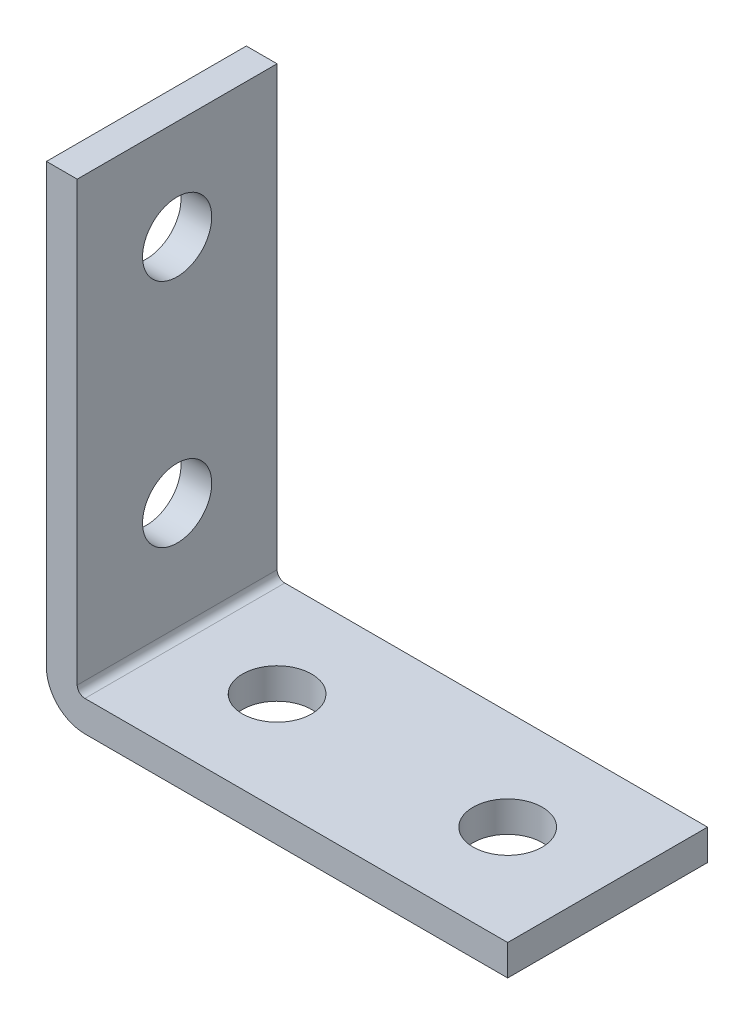
SolidWorks part; units mm, degrees
ref_plane "Front Plane" through (0, 0, 0) normal (0, 0, 1) x (1, 0, 0)
ref_plane "Top Plane" through (0, 0, 0) normal (0, 1, 0) x (1, 0, 0)
ref_plane "Right Plane" through (0, 0, 0) normal (1, 0, 0) x (0, 0, -1)
sketch "Sketch1" plane through (0, 0, 0) normal (0, 0, 1) x (1, 0, 0)
  line L0 (0, 98.425) -> (0, 7.9375)
  line L1 (7.9375, 0) -> (95.25, 0)
  arc A0 (0, 7.9375) -> (7.9375, 0) centre (7.9375, 7.9375) ccw
  dimension "D1" = 7.9375
  dimension "B" = 95.25
  dimension "A" = 98.425
extrude "Extrude-Thin1" add sketch "Sketch1" along normal mid plane 41.275 thin thin type one direction reverse wall 6.35
sketch "Sketch2" plane through (0, 6.35, 0) normal (0, 1, 0) x (1, 0, 0)
  line L0 (95.25, -20.6375) -> (95.25, 20.6375) construction
  circle A0 centre (74.6125, 0) radius 7.1438
  circle A1 centre (26.9875, 0) radius 7.1437
  dimension "Hole Size" = 14.2875
  dimension "edge" = 20.6375
  dimension "Spacing" = 47.625
extrude "Cut-Extrude1" cut sketch "Sketch2" against normal through all
sketch "Sketch3" plane through (6.35, 0, 0) normal (1, 0, 0) x (0, 0, -1)
  line L0 (-20.6375, 98.425) -> (20.6375, 98.425) construction
  circle A0 centre (0, 77.7875) radius 7.1438
  circle A1 centre (0, 30.1625) radius 7.1438
  dimension "D1" = 20.6375
  dimension "D2" = 14.2875
  dimension "D3" = 47.625
extrude "Cut-Extrude2" cut sketch "Sketch3" against normal through all
equation "\"D3@Sketch3\" = \"Spacing@Sketch2\""
equation "\"D2@Sketch3\" = \"Hole Size@Sketch2\""
